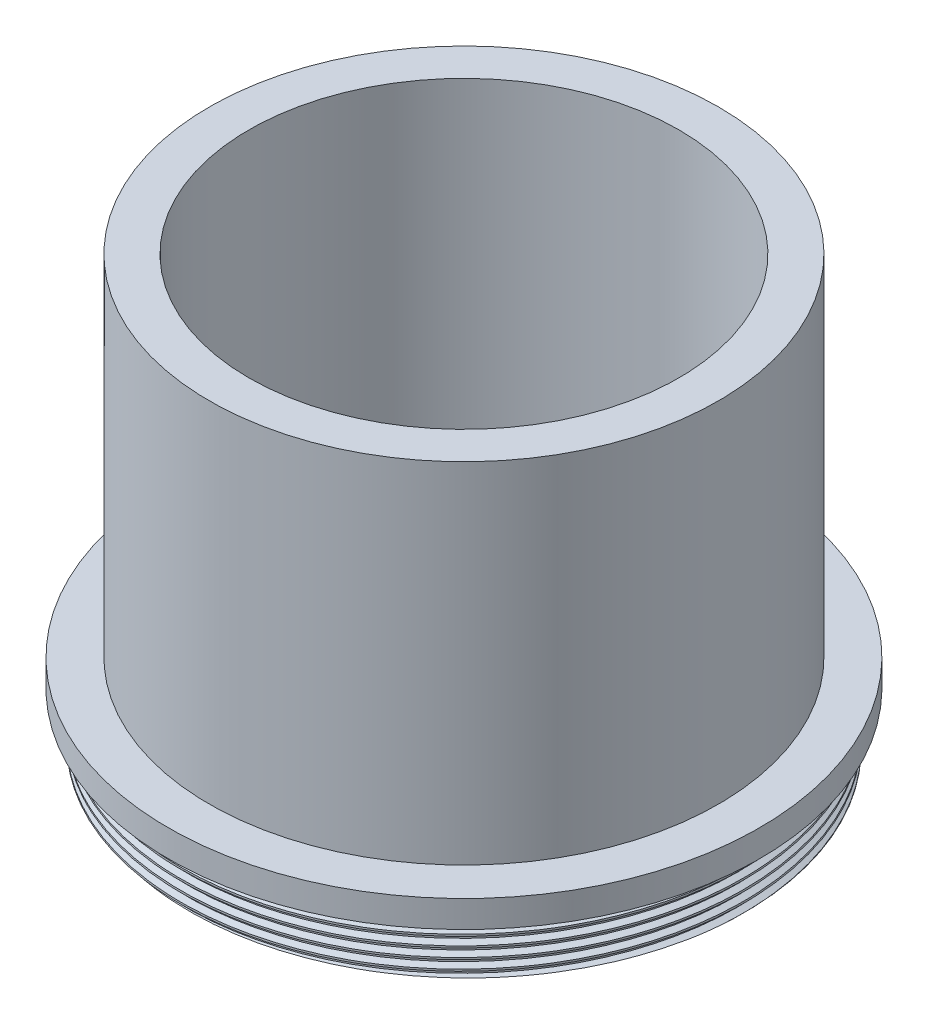
SolidWorks part; units mm, degrees
ref_plane "Front Plane" through (0, 0, 0) normal (0, 0, 1) x (1, 0, 0)
ref_plane "Top Plane" through (0, 0, 0) normal (0, 1, 0) x (1, 0, 0)
ref_plane "Right Plane" through (0, 0, 0) normal (1, 0, 0) x (0, 0, -1)
sketch "Sketch1" plane through (0, 0, 0) normal (0, 0, 1) x (1, 0, 0)
  line L0 (0, 0) -> (0, 23.5976) construction
  line L1 (-16, -0.0375) -> (-16, 31.9625)
  line L2 (-16, 31.9625) -> (-18.95, 31.9625)
  line L3 (-18.95, 31.9625) -> (-18.95, 5.9625)
  line L4 (-18.95, 5.9625) -> (-22, 5.9625)
  line L5 (-22, 5.9625) -> (-22, 3.9625)
  line L6 (-22, 3.9625) -> (-20.9, 3.9625)
  line L7 (-20.9, 3.9625) -> (-20.9, -0.0375)
  line L8 (-20.9, -0.0375) -> (-16, -0.0375)
  dimension "D1" = 18.95
  dimension "D2" = 32
  dimension "D3" = 2
  dimension "D4" = 6
  dimension "D5" = 22
  dimension "D6" = 16
  dimension "D7" = 20.9
revolve "Revolve1" add sketch "Sketch1" angle 360 about L0
thread "Thread2" pitch 0.7 method cut profile "Thread Profile2" start angle 0, offset 0, length 42, pitch 0.75, diameter 41.8
ref_plane "Plane2" through (-20.9, 3.9625, 0) normal (0, 0, 1) x (-1, 0, 0)
sketch "Thread Profile2" plane through (-20.9, 3.9625, 0) normal (0, 0, 1) x (-1, 0, 0)
  line L0 (0, 0) -> (0, 0.7) construction
  line L11 (0, 0) -> (0, 0.6125)
  line L12 (0, 0.6125) -> (-0.3789, 0.3937)
  line L13 (-0.3789, 0.3937) -> (-0.3789, 0.2187)
  line L15 (-0.3789, 0.2187) -> (0, 0)
  line L17 (-0.3789, 0.3062) -> (0, 0.3062) construction
  point P2 (0, 0)
  dimension "Pitch" = 0.7
  dimension "Profile_Angle" = 60
  dimension "Profile_Land" = 0.175
  dimension "Profile_Height" = 0.3789
